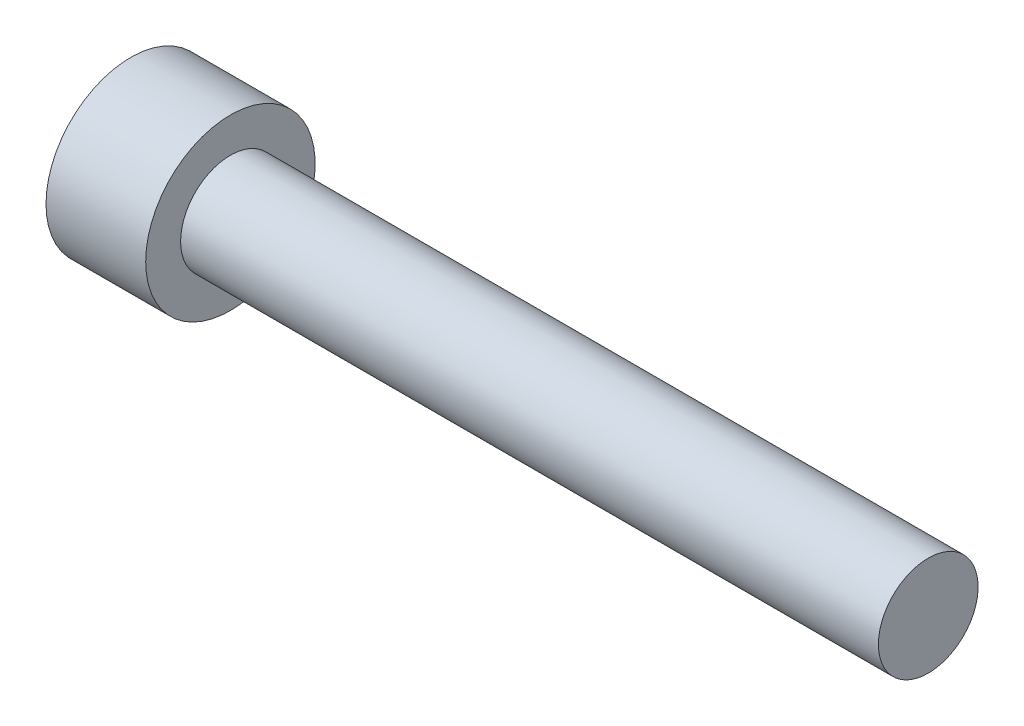
SolidWorks part; units mm, degrees
ref_plane "Front Plane" through (0, 0, 0) normal (0, 0, 1) x (1, 0, 0)
ref_plane "Top Plane" through (0, 0, 0) normal (0, 1, 0) x (1, 0, 0)
ref_plane "Right Plane" through (0, 0, 0) normal (1, 0, 0) x (0, 0, -1)
sketch "Screw Sketch" plane through (0, 0, 0) normal (0, 0, 1) x (1, 0, 0)
  line L0 (-1000, 0) -> (1000, 0) construction
  line L1 (-5, 0) -> (-5, 4.25)
  line L2 (-5, 4.25) -> (0, 4.25)
  line L3 (0, 4.25) -> (0, 2.5)
  line L4 (0, 2.5) -> (35, 2.5)
  line L5 (35, 2.5) -> (35, 0)
  line L6 (35, 0) -> (-5, 0)
revolve "Screw" add sketch "Screw Sketch" angle 360 about L0
ref_axis "Engine Axis" through (37, 0, 0) along (-1, 0, 0)
ref_plane "Head Top" through (-5, 0, 0) normal (1, 0, 0) x (0, 0, -1)
sketch "Socket Sketch" plane through (-5, 0, 0) normal (1, 0, 0) x (0, 0, -1)
  line L0 (2.3094, 0) -> (1.1547, 2)
  line L1 (1.1547, 2) -> (-1.1547, 2)
  line L2 (-1.1547, 2) -> (-2.3094, 0)
  line L3 (-2.3094, 0) -> (-1.1547, -2)
  line L4 (-1.1547, -2) -> (1.1547, -2)
  line L5 (1.1547, -2) -> (2.3094, 0)
extrude "Socket" cut sketch "Socket Sketch" along normal blind 2.5
